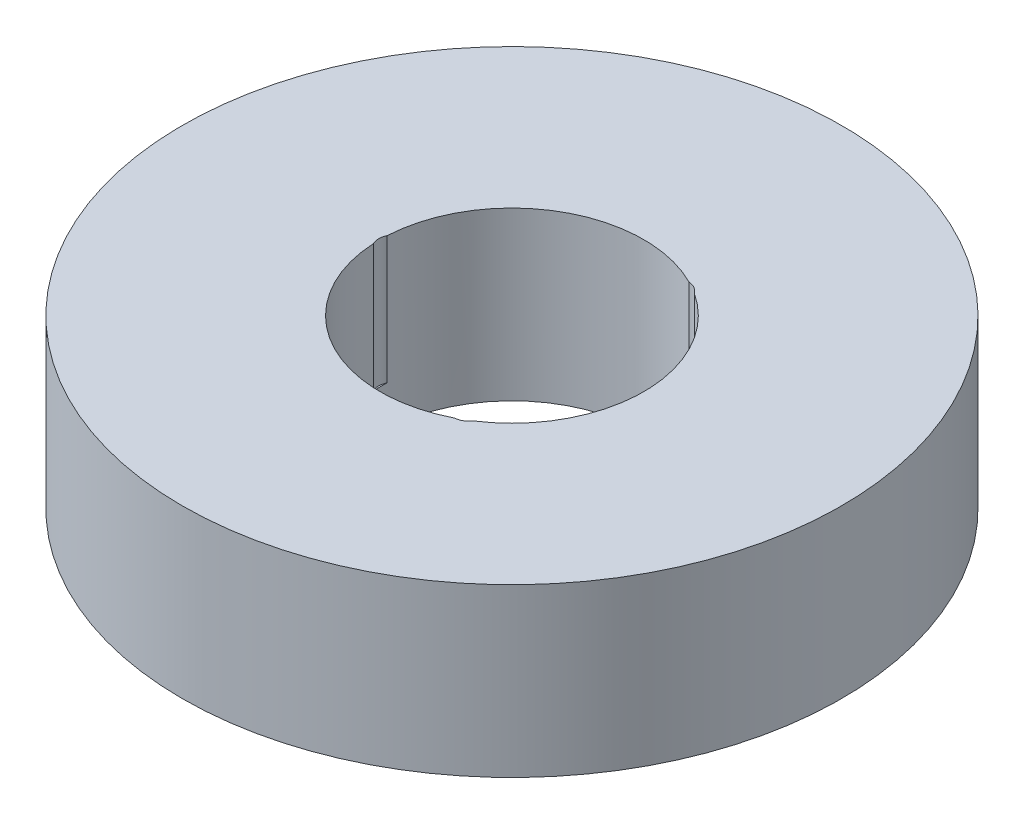
SolidWorks part; units mm, degrees
ref_plane "Front Plane" through (0, 0, 0) normal (0, 0, 1) x (1, 0, 0)
ref_plane "Top Plane" through (0, 0, 0) normal (0, 1, 0) x (1, 0, 0)
ref_plane "Right Plane" through (0, 0, 0) normal (1, 0, 0) x (0, 0, -1)
sketch "Sketch1" plane through (0, 0, 0) normal (0, 1, 0) x (1, 0, 0)
  circle A0 centre (0, 0) radius 37.5
  dimension "FLANGE_OD" = 75
extrude "Boss-Extrude1" add sketch "Sketch1" along normal blind 19
sketch "Sketch2" plane through (0, 0, 0) normal (0, 1, 0) x (1, 0, 0)
  circle A0 centre (0, 0) radius 15
  dimension "BORE_D" = 30
extrude "Cut-Extrude1" cut sketch "Sketch2" along normal through all
sketch "Sketch3" plane through (0, 19, 0) normal (0, 1, 0) x (1, 0, 0)
  circle A0 centre (0, 0) radius 13.3804 construction
  circle A1 centre (-13.3804, 0) radius 1.7815
  dimension "BOLT_D" = 3.5629
  dimension "BOLT_PCD" = 26.7608
extrude "Cut-Extrude2" cut sketch "Sketch3" against normal blind 14.5101
pattern_circular "CirPattern1" count 3 over 360 about axis through (0, 0, 0) along (0, 1, 0) of "Cut-Extrude2"
